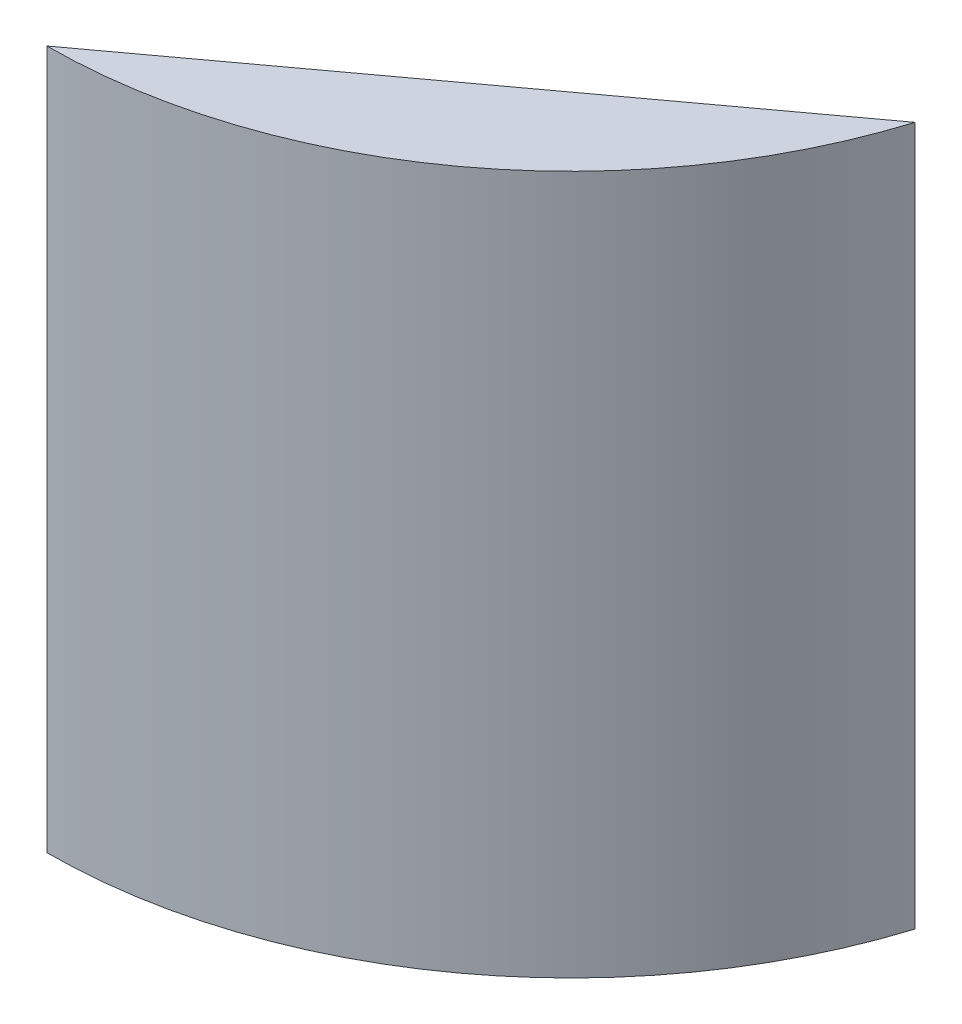
SolidWorks part; units mm, degrees
ref_plane "Front Plane" through (0, 0, 0) normal (0, 0, 1) x (1, 0, 0)
ref_plane "Top Plane" through (0, 0, 0) normal (0, 1, 0) x (1, 0, 0)
ref_plane "Right Plane" through (0, 0, 0) normal (1, 0, 0) x (0, 0, -1)
sketch "Sketch1" plane through (0, 0, 0) normal (0, 1, 0) x (1, 0, 0)
  circle A0 centre (0, 0) radius 85.725
extrude "Boss-Extrude1" add sketch "Sketch1" along normal blind 114.3
sketch "Sketch2" plane through (0, 114.3, 0) normal (0, 1, 0) x (1, 0, 0)
  line L0 (0, -85.725) -> (81.839, -25.5176)
  line L1 (81.839, -25.5176) -> (151.3047, 75.0629)
  line L2 (151.3047, 75.0629) -> (-38.5139, 115.9348)
  line L3 (-38.5139, 115.9348) -> (-149.3397, 18.864)
  line L4 (-149.3397, 18.864) -> (-68.7749, -104.5378)
  line L5 (-68.7749, -104.5378) -> (0, -85.725)
  circle A0 centre (0, 0) radius 85.725 construction
extrude "Cut-Extrude1" cut sketch "Sketch2" against normal blind 152.4
sketch "Sketch3" plane through (40.9195, 0, 55.6213) normal (-0.5926, 0, -0.8055) x (-0.8055, 0, 0.5926)
  line L0 (50.8, 0) -> (50.8, 114.3) construction
  line L1 (50.8, 0) -> (-50.8, 0) construction
  circle A0 centre (2.54, 104.14) radius 2.7781
  circle A1 centre (27.94, 104.14) radius 2.7781
  circle A2 centre (2.54, 27.94) radius 2.7781
  circle A3 centre (27.94, 27.94) radius 2.7781
  dimension "D1" = 22.86
  dimension "D2" = 76.2
  dimension "D3" = 27.94
  dimension "D4" = 76.2
  dimension "D5" = 25.4
  dimension "D6" = 25.4
extrude "Cut-Extrude2" cut sketch "Sketch3" against normal blind 7.9375
sketch "Sketch4" plane through (0, 0, 0) normal (0, -1, 0) x (-1, 0, 0)
  line L0 (-40.9195, -55.6213) -> (-50.8, -69.0517) construction
  line L1 (0, -85.725) -> (-81.839, -25.5176) construction
  circle A0 centre (-45.8598, -62.3365) radius 5.588
  arc A1 (-81.839, -25.5176) -> (0, -85.725) centre (0, 0) ccw construction
  point P6 (0, 0)
  point P7 (0, 0)
  point P8 (0, 0)
  dimension "D1" = 11.176
extrude "Cut-Extrude3" cut sketch "Sketch4" against normal blind 6.096
